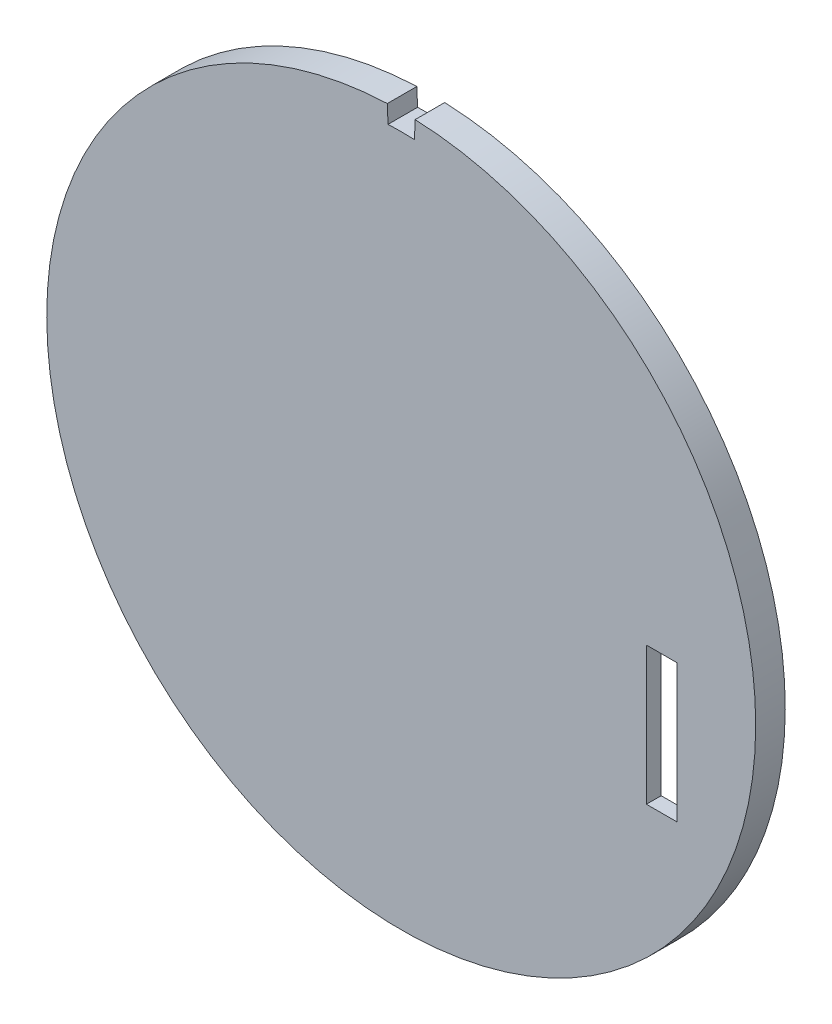
SolidWorks part; units mm, degrees
material "PMMA"
ref_plane "Front Plane" through (0, 0, 0) normal (0, 0, 1) x (1, 0, 0)
ref_plane "Top Plane" through (0, 0, 0) normal (0, 1, 0) x (1, 0, 0)
ref_plane "Right Plane" through (0, 0, 0) normal (1, 0, 0) x (0, 0, -1)
sketch "Sketch1" plane through (0, 0, 0) normal (0, 0, 1) x (1, 0, 0)
  line L0 (0, 45.9969) -> (0, -49.8146) construction
  line L1 (-28, 4.5) -> (28, 4.5)
  line L2 (28, 4.5) -> (28, -17)
  line L3 (28, -17) -> (21.5, -23.5)
  line L4 (21.5, -23.5) -> (-21.5, -23.5)
  line L5 (-21.5, -23.5) -> (-28, -17)
  line L6 (-28, -17) -> (-28, 4.5)
  line L7 (-1.4134, 35.9722) -> (-1.3427, 34.1736)
  line L8 (28, 1.5) -> (24.9, 1.5)
  line L9 (1.3427, 34.1736) -> (1.4134, 35.9722)
  line L10 (24.9, 1.5) -> (24.9, -12.5)
  line L11 (24.9, -12.5) -> (28, -12.5)
  arc A0 (-1.4134, 35.9722) -> (1.4134, 35.9722) centre (0, 0) ccw
  arc A1 (-1.3427, 34.1736) -> (1.3427, 34.1736) centre (0, 0) cw
  dimension "D1" = 72
  dimension "D9" = 34.2
  dimension "D10" = 3
  dimension "D2" = 56
  dimension "D3" = 21.5
  dimension "D4" = 135
  dimension "D5" = 28
  dimension "D6" = 135
  dimension "D7" = 4.5
  dimension "D8" = 4.5
  dimension "D11" = 17
  dimension "D12" = 3.1
extrude "Boss-Extrude3" add sketch "Sketch1" against normal blind 3 contours A1 L0 L1 L2 L3 L4 A0 L9 | L0 A1 L7 A0 L4 L5 L6 L1 region at (16.2721, 5.4394, 0) region at (-16.2721, 5.4394, 0)
extrude "Boss-Extrude4" add sketch "Sketch1<9>" against normal blind 1.5 contours L1 L0 L4 L3 L2 L11 L10 L8 | L0 L1 L6 L5 L4 region at (12.9015, -9.3938, 0) region at (-13.6723, -9.1723, 0)
sketch "Sketch1<9>" plane through (0, 0, 0) normal (0, 0, 1) x (1, 0, 0) same geometry as "Sketch1"
